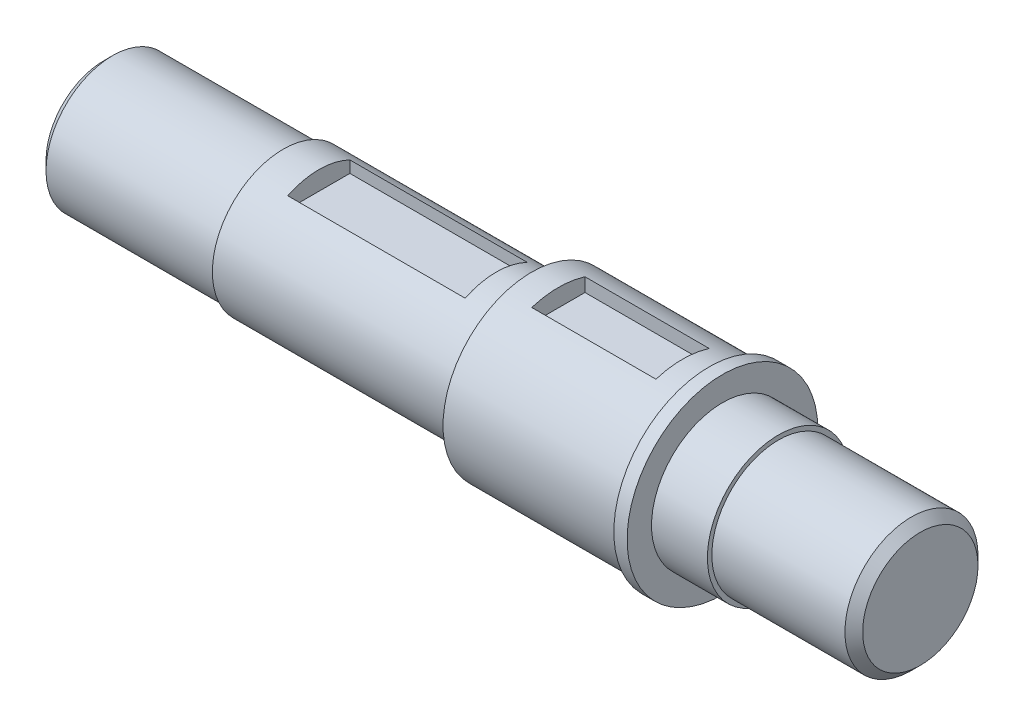
SolidWorks part; units mm, degrees
ref_plane "前视基准面" through (0, 0, 0) normal (0, 0, 1) x (1, 0, 0)
ref_plane "上视基准面" through (0, 0, 0) normal (0, 1, 0) x (1, 0, 0)
ref_plane "右视基准面" through (0, 0, 0) normal (1, 0, 0) x (0, 0, -1)
sketch "草图2" plane through (0, 0, 0) normal (0, 1, 0) x (1, 0, 0)
  line L0 (0, 0) -> (0, 15)
  line L1 (0, 15) -> (40.5, 15)
  line L2 (40.5, 15) -> (40.5, 16)
  line L3 (40.5, 16) -> (96.5, 16)
  line L4 (96.5, 16) -> (96.5, 20)
  line L5 (96.5, 20) -> (136.5, 20)
  line L6 (136.5, 20) -> (136.5, 21.5)
  line L7 (136.5, 21.5) -> (139.5, 21.5)
  line L8 (139.5, 21.5) -> (139.5, 16)
  line L9 (139.5, 16) -> (152.1, 16)
  line L10 (152.1, 16) -> (152.1, 15)
  line L11 (152.1, 15) -> (184.1, 15)
  line L12 (184.1, 15) -> (184.1, 0)
  line L13 (184.1, 0) -> (0, 0)
  dimension "D1" = 15
  dimension "D2" = 40.5
  dimension "D3" = 16
  dimension "D4" = 20
  dimension "D5" = 1.5
  dimension "D6" = 3
  dimension "D7" = 32
  dimension "D8" = 15
  dimension "D9" = 56
  dimension "D10" = 40
  dimension "D11" = 12.6
revolve "旋转1" add sketch "草图2" angle 360 about L13
chamfer "倒角1" distance 2 angle 45 2 edges at (184.1, 0, -15) (0, 0, -15)
sketch "草图3" plane through (0, 0, 0) normal (0, 1, 0) x (1, 0, 0)
  line L0 (0, 0) -> (40.5, 0)
  line L1 (40.5, 15) -> (40.5, -15) construction
  line L2 (40.5, 0) -> (96.5, 0)
  line L3 (96.5, 20) -> (96.5, -20) construction
  line L5 (48.5, 7) -> (88.5, 7)
  line L6 (48.5, 7) -> (48.5, -7)
  line L7 (48.5, -7) -> (88.5, -7)
  line L8 (88.5, 7) -> (88.5, -7)
  line L9 (68.5, -7) -> (68.5, 7) construction
  line L10 (48.5, 0) -> (88.5, 0) construction
  point P5 (68.5, 0)
  dimension "D1" = 40
  dimension "D2" = 14
extrude "切除-拉伸1" cut sketch "草图3" along normal blind 25 from offset 11.75 contours L8 L5 L6 L2 | L8 L2 L6 L7 region at (68.5, 0, -3.5) region at (68.5, 0, 3.5)
sketch "草图4" plane through (0, 0, 0) normal (0, 1, 0) x (1, 0, 0)
  line L0 (96.5, 0) -> (136.5, 0)
  line L1 (96.5, 20) -> (96.5, -20) construction
  line L2 (136.5, 20) -> (136.5, -20) construction
  line L4 (102.5, 6) -> (130.5, 6)
  line L5 (102.5, 6) -> (102.5, -6)
  line L6 (102.5, -6) -> (130.5, -6)
  line L7 (130.5, 6) -> (130.5, -6)
  line L8 (116.5, -6) -> (116.5, 6) construction
  line L9 (102.5, 0) -> (130.5, 0) construction
  point P6 (116.5, 0)
  dimension "D1" = 28
  dimension "D2" = 12
extrude "切除-拉伸2" cut sketch "草图4" along normal blind 11 from offset 16 contours L7 L4 L5 L0 | L7 L0 L5 L6 region at (116.5, 0, -3) region at (116.5, 0, 3)
sketch "草图5" plane through (184.1, 0, 0) normal (1, 0, 0) x (0, 0, -1)
  line L0 (0, 0) -> (0, 13)
  circle A0 centre (0, 0) radius 13 construction
sketch "草图7" plane through (0, 0, 0) normal (-1, 0, 0) x (0, 0, 1)
  line L0 (0, 0) -> (0, -13)
  circle A0 centre (0, 0) radius 13 construction
